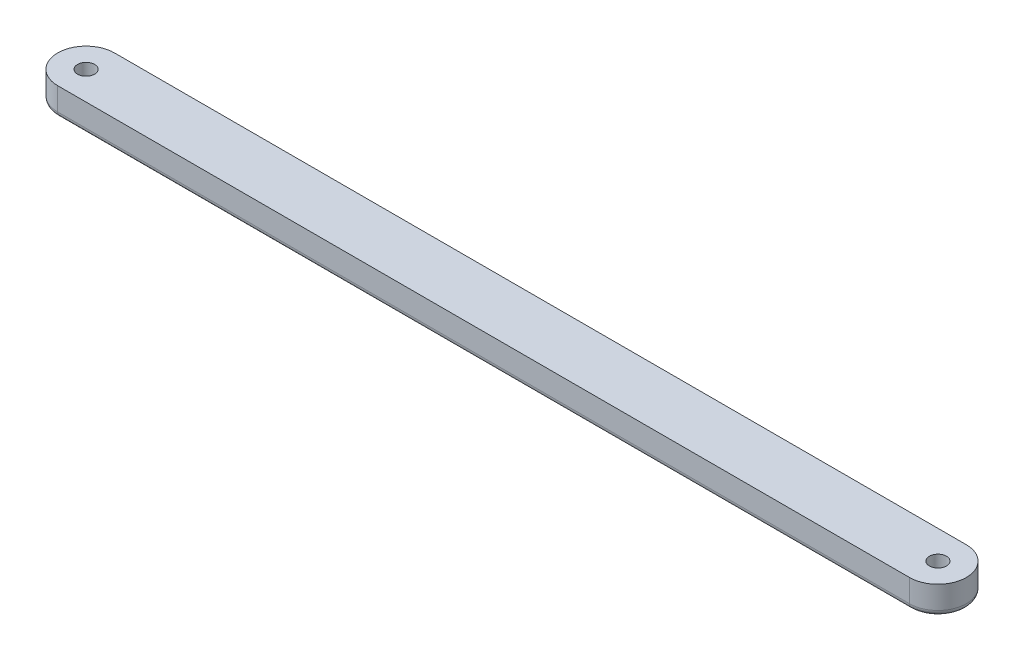
SolidWorks part; units mm, degrees
ref_plane "Front Plane" through (0, 0, 0) normal (0, 0, 1) x (1, 0, 0)
ref_plane "Top Plane" through (0, 0, 0) normal (0, 1, 0) x (1, 0, 0)
ref_plane "Right Plane" through (0, 0, 0) normal (1, 0, 0) x (0, 0, -1)
sketch "Sketch1" plane through (0, 0, 0) normal (0, 1, 0) x (1, 0, 0)
  line L0 (0, 0) -> (150, 0) construction
  line L1 (0, 5) -> (150, 5)
  line L2 (0, -5) -> (150, -5)
  line L3 (0, 5) -> (0, -5) construction
  circle A0 centre (0, 0) radius 1.5
  circle A1 centre (150, 0) radius 1.5
  circle A2 centre (0, 0) radius 5
  circle A3 centre (150, 0) radius 5
  dimension "D1" = 3
  dimension "D2" = 3
  dimension "D3" = 10
  dimension "D4" = 10
  dimension "D5" = 150
  dimension "D6" = 10
extrude "Boss-Extrude1" add sketch "Sketch1" along normal blind 5 contours A2 L0 A3 L1 | L0 A2 L2 A3 | A0 A2 | A3 A1 region at (75, 0, 0) region at (3.4355, 0, -3.4355) region at (153.4355, 0, -3.4355)
fillet "Fillet1" radius 1 4 edges at (155, 0, 0) (75, 0, -5) (-5, 0, 0) (75, 0, 5)
